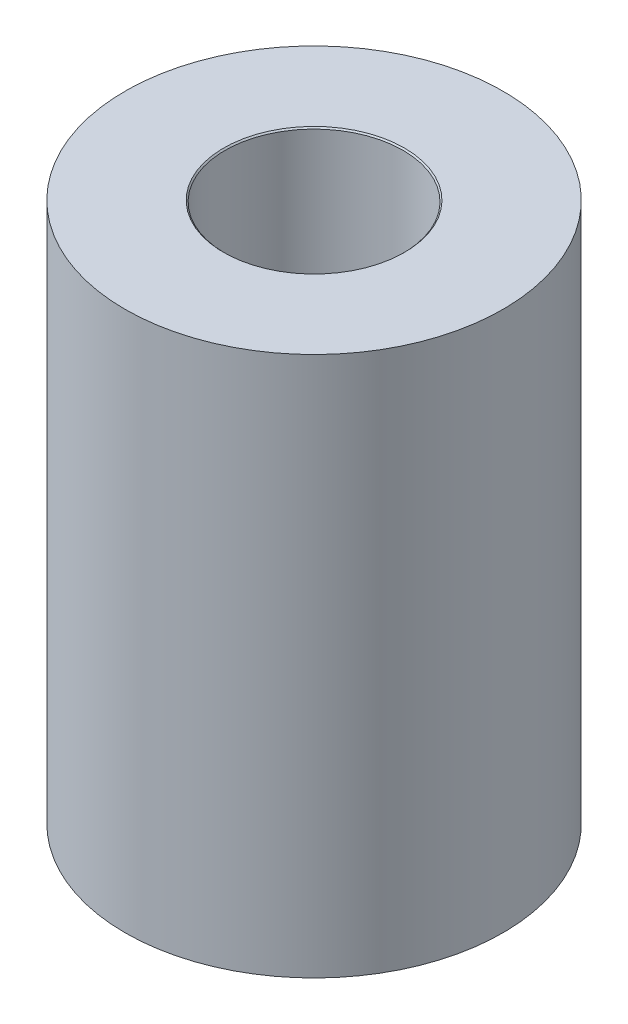
SolidWorks part; units mm, degrees
note: '?' marks a value the reader was unsure of.
material "6061-T6 (SS)"
ref_plane "Front Plane" through (0, 0, 0) normal (0, 0, 1) x (1, 0, 0)
ref_plane "Top Plane" through (0, 0, 0) normal (0, 1, 0) x (1, 0, 0)
ref_plane "Right Plane" through (0, 0, 0) normal (1, 0, 0) x (0, 0, -1)
other "Configuration Table"
ref_axis "FASTENER" through (0, -0.4, 0) along (0, 1, 0)?
sketch "Sketch1" plane through (0, 0, 0) normal (0, 1, 0) x (1, 0, 0)
  circle A0 centre (0, 0) radius 3.5
  dimension "D1" = 7
extrude "Boss-Extrude1" add sketch "Sketch1" along normal blind 10
hole_wizard "M4 Clearance Hole1" [suppressed] positions "Sketch2" profile "Sketch3" hole size "M4" standard "ISO"
sketch "Sketch2" plane through (0, 10, 0) normal (0, 1, 0) x (1, 0, 0)
  point P0 (0, 0)
sketch "Sketch3" plane through (0, 10, 0) normal (1, 0, 0) x (0, 0, 1)
  line L0 (0, 0) -> (0, 10)
  line L1 (0, 10) -> (2.25, 10)
  line L2 (2.25, 10) -> (2.25, 0)
  line L5 (2.25, 0) -> (0, 0)
  line L11 (0, -6.35) -> (0, 107.95) construction
  dimension "Thru Hole Dia." = 4.5
  dimension "Thru Hole Depth" = 10
hole_wizard "Tap Drill for M4 Tap1" positions "Sketch4" profile "Sketch5" hole size "M4" standard "ISO" end condition through all
sketch "Sketch4" plane through (0, 0, 0) normal (0, -1, 0) x (-1, 0, 0)
  point P0 (0, 0)
sketch "Sketch5" plane through (0, 0, 0) normal (1, 0, 0) x (0, 0, -1)
  line L0 (0, 0) -> (0, 10)
  line L1 (0, 10) -> (1.675, 10)
  line L2 (1.65, 9.975) -> (1.65, 0.1)
  line L3 (1.65, 0.1) -> (1.75, 0)
  line L5 (1.75, 0) -> (0, 0)
  line L6 (-1.65, 0.1) -> (-1.75, 0) construction
  line L7 (1.675, 10) -> (1.65, 9.975)
  line L8 (-1.675, 10) -> (-1.65, 9.975) construction
  line L11 (0, -6.35) -> (0, 107.95) construction
  dimension "Thru Hole Dia." = 3.3
  dimension "Thru Hole Depth" = 10
  dimension "Near C'Sink Dia." = 3.5
  dimension "Near C'Sink Angle" = 90
  dimension "Far C'Sink Dia." = 3.35
  dimension "Far C'Sink Angle" = 90
